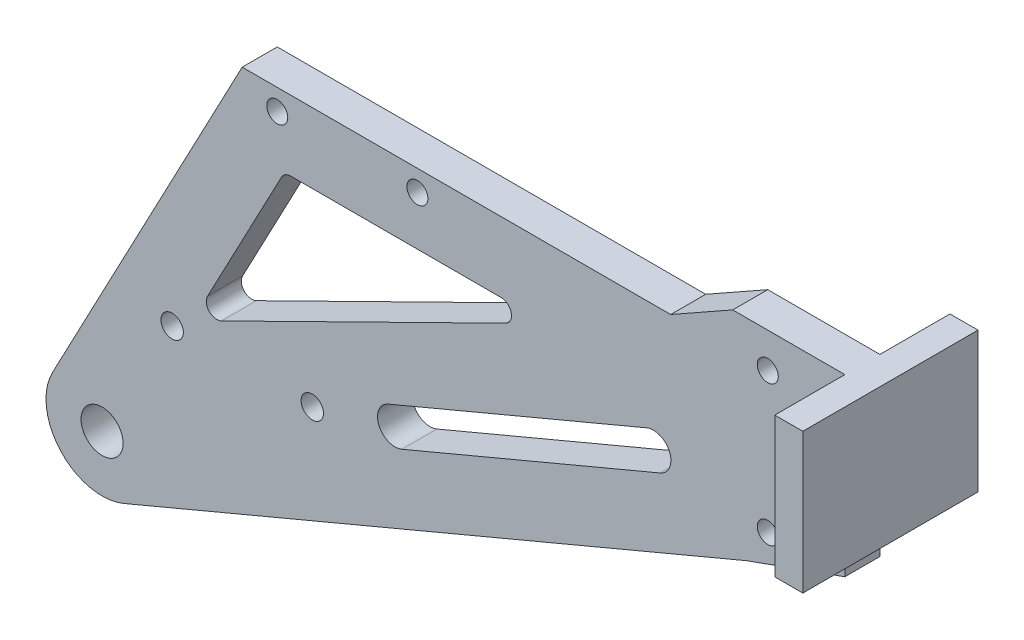
SolidWorks part; units mm, degrees
material "ABS"
ref_plane "前视基准面" through (0, 0, 0) normal (0, 0, 1) x (1, 0, 0)
ref_plane "上视基准面" through (0, 0, 0) normal (0, 1, 0) x (1, 0, 0)
ref_plane "右视基准面" through (0, 0, 0) normal (1, 0, 0) x (0, 0, -1)
sketch "草图1" plane through (0, 0, 0) normal (0, 0, 1) x (1, 0, 0)
  line L0 (-3.9331, 6.9664) -> (90, 60)
  line L1 (90, 60) -> (130, 60)
  line L2 (130, 60) -> (130, 30)
  line L3 (92, 30) -> (3.1005, -7.3748)
  line L4 (92, 30) -> (130, 30)
  line L5 (125, 55) -> (95, 55) construction
  line L6 (125, 55) -> (125, 35) construction
  line L7 (125, 35) -> (95, 35) construction
  line L8 (95, 55) -> (95, 35) construction
  circle A0 centre (0, 0) radius 3
  arc A1 (-3.9331, 6.9664) -> (3.1005, -7.3748) centre (0, 0) ccw
  circle A2 centre (95, 55) radius 1.5
  circle A3 centre (125, 55) radius 1.5
  circle A4 centre (125, 35) radius 1.5
  circle A5 centre (95, 35) radius 1.5
  dimension "D1" = 6
  dimension "D2" = 40
  dimension "D6" = 8
  dimension "D7" = 5
  dimension "D11" = 3
  dimension "D3" = 30
  dimension "D4" = 60
  dimension "D5" = 90
  dimension "D8" = 5
  dimension "D9" = 5
  dimension "D10" = 5
  dimension "D12" = 3
extrude "凸台-拉伸1" add sketch "草图1" along normal blind 5
sketch "草图3" plane through (0, 0, 5) normal (0, 0, 1) x (1, 0, 0)
  line L0 (81.144, 55) -> (20, 55)
  line L1 (90, 60) -> (-3.9331, 6.9664) construction
  line L2 (20, 55) -> (20, 20.4788)
  line L3 (20, 20.4788) -> (81.144, 55)
  line L4 (92, 30) -> (130, 30) construction
  circle A0 centre (95, 55) radius 1.5 construction
  dimension "D1" = 25
  dimension "D2" = 75
extrude "凸台-拉伸2" add sketch "草图3" against normal up to surface (5 mm away) up to face at (72.4002, 29.3788, 0)
sketch "草图4" plane through (0, 0, 5) normal (0, 0, 1) x (1, 0, 0)
  line L0 (25, 52) -> (45, 52) construction
  line L1 (81.144, 55) -> (20, 55) construction
  circle A0 centre (25, 52) radius 1.5
  circle A1 centre (45, 52) radius 1.5
  circle A2 centre (95, 55) radius 1.5 construction
  dimension "D1" = 3
  dimension "D4" = 3
  dimension "D2" = 20
  dimension "D3" = 50
extrude "切除-拉伸1" cut sketch "草图4" against normal through all
sketch "草图6" plane through (0, 0, 5) normal (0, 0, 1) x (1, 0, 0)
  line L0 (-7.074, 3.736) -> (20, 55)
  line L1 (20, 55) -> (20, 20.4788) construction
  line L2 (20, 20.4788) -> (-3.9331, 6.9664) construction
  line L3 (20, 55) -> (20, 20.4788)
  line L4 (20, 20.4788) -> (-3.9331, 6.9664)
  arc A0 (-3.9331, 6.9664) -> (3.1005, -7.3748) centre (0, 0) ccw construction
  arc A1 (-3.9331, 6.9664) -> (-7.074, 3.736) centre (0, 0) ccw
extrude "凸台-拉伸3" add sketch "草图6" against normal up to surface (5 mm away) up to face at (26.5, 52, 0)
sketch "草图5" plane through (0, 0, 5) normal (0, 0, 1) x (1, 0, 0)
  line L3 (20, 55) -> (-7.074, 3.736) construction
  line L10 (81.144, 55) -> (20, 55) construction
  line L12 (95, 55) -> (125, 55) construction
  line L13 (95, 55) -> (95, 35) construction
  line L14 (95, 35) -> (125, 35) construction
  line L15 (125, 55) -> (125, 35) construction
  line L21 (25.6054, 44.2005) -> (15.0428, 24.2005)
  line L22 (17.0325, 22.1546) -> (57.5951, 42.1546)
  line L24 (56.9318, 45) -> (26.9318, 45)
  arc A13 (57.5951, 42.1546) -> (56.9318, 45) centre (56.9318, 43.5) ccw
  arc A14 (15.0428, 24.2005) -> (17.0325, 22.1546) centre (16.3692, 23.5) ccw
  arc A15 (25.6054, 44.2005) -> (26.9318, 45) centre (26.9318, 43.5) cw
  point P15 (0, 0)
  dimension "D3" = 10
  dimension "D4" = 1.5
  dimension "D8" = 30
  dimension "D2" = 10
  dimension "D12" = 20
extrude "切除-拉伸2" cut sketch "草图5" against normal through all
sketch "草图7" plane through (0, 0, 5) normal (0, 0, 1) x (1, 0, 0)
  line L0 (10, 18) -> (30, 18) construction
  circle A0 centre (10, 18) radius 1.6
  circle A1 centre (30, 18) radius 1.6
  dimension "D2" = 3.2
  dimension "D1" = 20
  dimension "D3" = 10
  dimension "D4" = 18
extrude "切除-拉伸3" cut sketch "草图7" against normal through all
sketch "草图8" plane through (130, 0, 0) normal (1, 0, 0) x (0, 0, -1)
  line L0 (0, 30) -> (-5, 30)
  line L1 (-5, 30) -> (-15, 30)
  line L2 (-15, 30) -> (-15, 60)
  line L3 (-15, 60) -> (10, 60)
  line L4 (10, 60) -> (10, 30)
  line L5 (10, 30) -> (0, 30)
extrude "凸台-拉伸4" add sketch "草图8" against normal blind 24
sketch "草图10" plane through (0, 0, 5) normal (0, 0, 1) x (1, 0, 0)
  line L0 (130, 30) -> (130, 40)
  line L1 (130, 60) -> (130, 30) construction
  line L2 (130, 40) -> (119.911, 40)
  line L5 (92, 30) -> (130, 30)
  line L6 (130, 30) -> (130, 40)
  line L7 (119.911, 40) -> (92, 30)
  line M1 (106, 30) -> (106, 60)
  line M8 (92, 30) -> (106, 30)
extrude "切除-拉伸4" cut sketch "草图10" against normal through all and the other way blind 10 contours L2 M8 M1 | L5 L0 L2 M1 region at (119.2431, 34.4363, 5) region at (101.3333, 31.672, 5)
sketch "草图12" plane through (0, 0, 5) normal (0, 0, 1) x (1, 0, 0)
  line L0 (37.3138, 32.1546) -> (46.2976, 10.786)
  line L1 (17.0325, 22.1546) -> (57.5951, 42.1546) construction
  line L2 (3.1005, -7.3748) -> (92, 30) construction
  line L3 (41.8057, 21.4703) -> (78.6795, 36.9726)
  line L4 (41.8057, 21.4703) -> (78.6795, 36.9726) construction
  line L5 (40.8368, 23.7749) -> (77.7106, 39.2773)
  line L6 (42.7746, 19.1657) -> (79.6484, 34.668)
  arc A0 (40.8368, 23.7749) -> (42.7746, 19.1657) centre (41.8057, 21.4703) ccw
  arc A1 (79.6484, 34.668) -> (77.7106, 39.2773) centre (78.6795, 36.9726) ccw
  point P8 (60.2426, 29.2215)
extrude "切除-拉伸5" cut sketch "草图12" against normal through all contours L6 A1 L5 L0 | L0 A0 region at (59.4487, 31.1097, 5) region at (40.8276, 21.0591, 5)
sketch "草图14" plane through (0, 0, 15) normal (0, 0, 1) x (1, 0, 0)
  line L0 (130, 40) -> (106, 40)
  line L2 (106, 60) -> (106, 35.0159) construction
  line L3 (106, 40) -> (106, 35.0159)
  line L4 (106, 35.0159) -> (119.911, 40)
  line L5 (119.911, 40) -> (119.911, 60)
  line L6 (106, 60) -> (130, 60) construction
  line L7 (106, 60) -> (110, 60)
  line L8 (110, 60) -> (110, 40)
  line L9 (119.911, 60) -> (110, 60)
  line M1 (106, 35.0159) -> (119.911, 40)
  line M2 (119.911, 40) -> (130, 40)
  line M3 (130, 40) -> (130, 60)
  line M4 (130, 60) -> (106, 60)
  line M5 (106, 60) -> (106, 35.0159)
extrude "切除-拉伸7" cut sketch "草图14" against normal through all contours L0 M1 M5 | L8 L0 L5 M4 | L5 M2 M3 M4 region at (124.9555, 50, 15) region at (110.637, 38.3386, 15) region at (114.9555, 50, 15)
